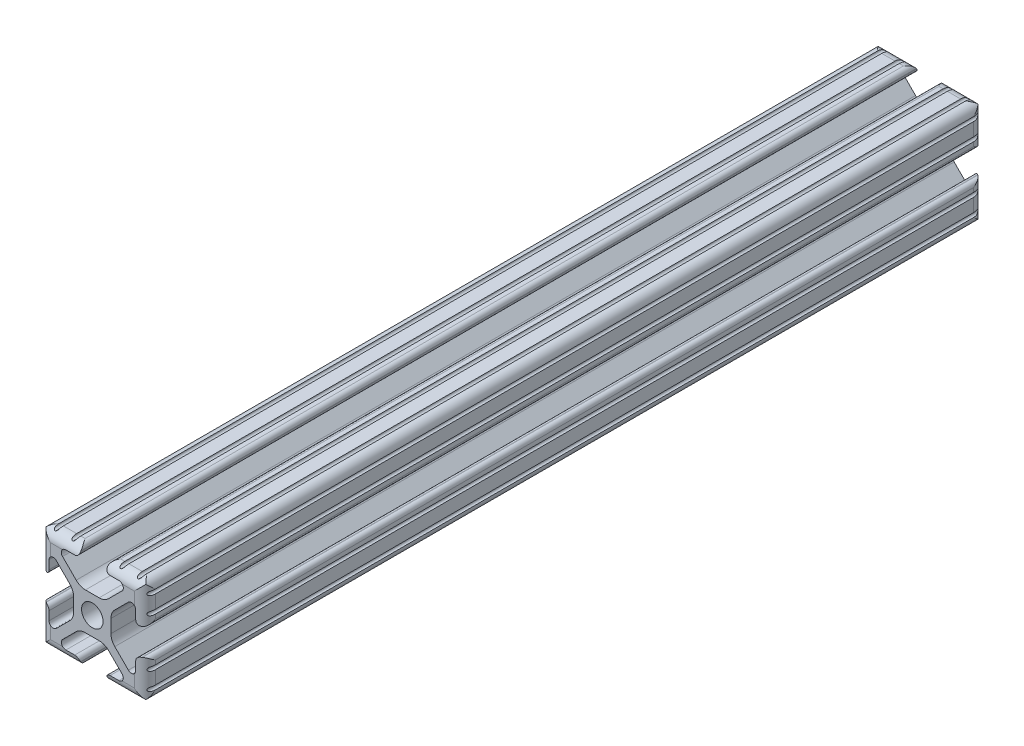
SolidWorks part; units mm, degrees
material "6061 Alloy"
ref_plane "Front Plane" through (0, 0, 0) normal (0, 0, 1) x (1, 0, 0)
ref_plane "Top Plane" through (0, 0, 0) normal (0, 1, 0) x (1, 0, 0)
ref_plane "Right Plane" through (0, 0, 0) normal (1, 0, 0) x (0, 0, -1)
sketch "Sketch1" plane through (0, 0, 0) normal (0, 0, 1) x (1, 0, 0)
  line L88 (-7.1797, -8.6452) -> (-3.9523, -5.4237)
  line L89 (-1.7093, -4.4958) -> (1.7093, -4.4958)
  line L90 (3.9523, -5.4237) -> (7.1797, -8.6452)
  line L91 (6.4164, -10.4902) -> (4.2875, -10.4902)
  line L92 (3.2385, -11.5392) -> (3.2385, -11.651)
  line L93 (4.2875, -12.7) -> (5.3171, -12.7)
  line L94 (6.3331, -12.7) -> (9.5504, -12.7)
  line L95 (12.7, -9.5504) -> (12.7, -6.3331)
  line L96 (12.7, -5.3171) -> (12.7, -4.2875)
  line L97 (11.651, -3.2385) -> (11.5392, -3.2385)
  line L98 (10.4902, -4.2875) -> (10.4902, -6.4021)
  line L99 (8.7371, -7.1294) -> (5.441, -3.8408)
  line L100 (4.5085, -1.5932) -> (4.5085, 1.5932)
  line L101 (5.441, 3.8408) -> (8.7371, 7.1294)
  line L102 (10.4902, 6.4021) -> (10.4902, 4.2875)
  line L103 (11.5392, 3.2385) -> (11.651, 3.2385)
  line L104 (12.7, 4.2875) -> (12.7, 5.3171)
  line L105 (12.7, 6.3331) -> (12.7, 9.5504)
  line L106 (9.5504, 12.7) -> (6.3331, 12.7)
  line L107 (5.3171, 12.7) -> (4.2875, 12.7)
  line L108 (3.2385, 11.651) -> (3.2385, 11.5392)
  line L109 (4.2875, 10.4902) -> (6.4768, 10.4902)
  line L110 (7.207, 8.7244) -> (3.8983, 5.4232)
  line L111 (1.6558, 4.4958) -> (-1.6558, 4.4958)
  line L112 (-3.8983, 5.4232) -> (-7.207, 8.7244)
  line L113 (-6.4768, 10.4902) -> (-4.2875, 10.4902)
  line L114 (-3.2385, 11.5392) -> (-3.2385, 11.651)
  line L115 (-4.2875, 12.7) -> (-5.3171, 12.7)
  line L116 (-6.3331, 12.7) -> (-9.5504, 12.7)
  line L117 (-12.7, 9.5504) -> (-12.7, 6.3331)
  line L118 (-12.7, 5.3171) -> (-12.7, 4.2875)
  line L119 (-11.651, 3.2385) -> (-11.5392, 3.2385)
  line L120 (-10.4902, 4.2875) -> (-10.4902, 6.4021)
  line L121 (-8.7371, 7.1294) -> (-5.441, 3.8408)
  line L122 (-4.5085, 1.5932) -> (-4.5085, -1.5932)
  line L123 (-5.441, -3.8408) -> (-8.7371, -7.1294)
  line L124 (-10.4902, -6.4021) -> (-10.4902, -4.2875)
  line L125 (-11.5392, -3.2385) -> (-11.651, -3.2385)
  line L126 (-12.7, -4.2875) -> (-12.7, -5.3171)
  line L127 (-12.7, -6.3331) -> (-12.7, -9.5504)
  line L128 (-9.5504, -12.7) -> (-6.3331, -12.7)
  line L129 (-5.3171, -12.7) -> (-4.2875, -12.7)
  line L130 (-3.2385, -11.651) -> (-3.2385, -11.5392)
  line L131 (-4.2875, -10.4902) -> (-6.4164, -10.4902)
  circle A1 centre (0, 0) radius 2.6035
  arc A104 (-7.1797, -8.6452) -> (-6.4164, -10.4902) centre (-6.4164, -9.4098) ccw
  arc A105 (-1.7093, -4.4958) -> (-3.9523, -5.4237) centre (-1.7093, -7.6708) ccw
  arc A106 (3.9523, -5.4237) -> (1.7093, -4.4958) centre (1.7093, -7.6708) ccw
  arc A107 (6.4164, -10.4902) -> (7.1797, -8.6452) centre (6.4164, -9.4098) ccw
  arc A108 (4.2875, -10.4902) -> (3.2385, -11.5392) centre (4.2875, -11.5392) ccw
  arc A109 (3.2385, -11.651) -> (4.2875, -12.7) centre (4.2875, -11.651) ccw
  arc A110 (6.3331, -12.7) -> (5.3171, -12.7) centre (5.8251, -12.7) ccw
  arc A111 (10.5664, -12.6998) -> (9.5504, -12.7) centre (10.0584, -12.7) ccw
  arc A112 (10.5664, -12.6998) -> (12.6998, -10.5664) centre (10.5918, -10.5918) ccw
  arc A113 (12.7, -9.5504) -> (12.6998, -10.5664) centre (12.7, -10.0584) ccw
  arc A114 (12.7, -5.3171) -> (12.7, -6.3331) centre (12.7, -5.8251) ccw
  arc A115 (12.7, -4.2875) -> (11.651, -3.2385) centre (11.651, -4.2875) ccw
  arc A116 (11.5392, -3.2385) -> (10.4902, -4.2875) centre (11.5392, -4.2875) ccw
  arc A117 (8.7371, -7.1294) -> (10.4902, -6.4021) centre (9.4628, -6.4021) ccw
  arc A118 (4.5085, -1.5932) -> (5.441, -3.8408) centre (7.6835, -1.5932) ccw
  arc A119 (5.441, 3.8408) -> (4.5085, 1.5932) centre (7.6835, 1.5932) ccw
  arc A120 (10.4902, 6.4021) -> (8.7371, 7.1294) centre (9.4628, 6.4021) ccw
  arc A121 (10.4902, 4.2875) -> (11.5392, 3.2385) centre (11.5392, 4.2875) ccw
  arc A122 (11.651, 3.2385) -> (12.7, 4.2875) centre (11.651, 4.2875) ccw
  arc A123 (12.7, 6.3331) -> (12.7, 5.3171) centre (12.7, 5.8251) ccw
  arc A124 (12.6998, 10.5664) -> (12.7, 9.5504) centre (12.7, 10.0584) ccw
  arc A125 (12.6998, 10.5664) -> (10.5664, 12.6998) centre (10.5918, 10.5918) ccw
  arc A126 (9.5504, 12.7) -> (10.5664, 12.6998) centre (10.0584, 12.7) ccw
  arc A127 (5.3171, 12.7) -> (6.3331, 12.7) centre (5.8251, 12.7) ccw
  arc A128 (4.2875, 12.7) -> (3.2385, 11.651) centre (4.2875, 11.651) ccw
  arc A129 (3.2385, 11.5392) -> (4.2875, 10.4902) centre (4.2875, 11.5392) ccw
  arc A130 (7.207, 8.7244) -> (6.4768, 10.4902) centre (6.4768, 9.4563) ccw
  arc A131 (1.6558, 4.4958) -> (3.8983, 5.4232) centre (1.6558, 7.6708) ccw
  arc A132 (-3.8983, 5.4232) -> (-1.6558, 4.4958) centre (-1.6558, 7.6708) ccw
  arc A133 (-6.4768, 10.4902) -> (-7.207, 8.7244) centre (-6.4768, 9.4563) ccw
  arc A134 (-4.2875, 10.4902) -> (-3.2385, 11.5392) centre (-4.2875, 11.5392) ccw
  arc A135 (-3.2385, 11.651) -> (-4.2875, 12.7) centre (-4.2875, 11.651) ccw
  arc A136 (-6.3331, 12.7) -> (-5.3171, 12.7) centre (-5.8251, 12.7) ccw
  arc A137 (-10.5664, 12.6998) -> (-9.5504, 12.7) centre (-10.0584, 12.7) ccw
  arc A138 (-10.5664, 12.6998) -> (-12.6998, 10.5664) centre (-10.5918, 10.5918) ccw
  arc A139 (-12.7, 9.5504) -> (-12.6998, 10.5664) centre (-12.7, 10.0584) ccw
  arc A140 (-12.7, 5.3171) -> (-12.7, 6.3331) centre (-12.7, 5.8251) ccw
  arc A141 (-12.7, 4.2875) -> (-11.651, 3.2385) centre (-11.651, 4.2875) ccw
  arc A142 (-11.5392, 3.2385) -> (-10.4902, 4.2875) centre (-11.5392, 4.2875) ccw
  arc A143 (-8.7371, 7.1294) -> (-10.4902, 6.4021) centre (-9.4628, 6.4021) ccw
  arc A144 (-4.5085, 1.5932) -> (-5.441, 3.8408) centre (-7.6835, 1.5932) ccw
  arc A145 (-5.441, -3.8408) -> (-4.5085, -1.5932) centre (-7.6835, -1.5932) ccw
  arc A146 (-10.4902, -6.4021) -> (-8.7371, -7.1294) centre (-9.4628, -6.4021) ccw
  arc A147 (-10.4902, -4.2875) -> (-11.5392, -3.2385) centre (-11.5392, -4.2875) ccw
  arc A148 (-11.651, -3.2385) -> (-12.7, -4.2875) centre (-11.651, -4.2875) ccw
  arc A149 (-12.7, -6.3331) -> (-12.7, -5.3171) centre (-12.7, -5.8251) ccw
  arc A150 (-12.6998, -10.5664) -> (-12.7, -9.5504) centre (-12.7, -10.0584) ccw
  arc A151 (-12.6998, -10.5664) -> (-10.5664, -12.6998) centre (-10.5918, -10.5918) ccw
  arc A152 (-9.5504, -12.7) -> (-10.5664, -12.6998) centre (-10.0584, -12.7) ccw
  arc A153 (-5.3171, -12.7) -> (-6.3331, -12.7) centre (-5.8251, -12.7) ccw
  arc A154 (-4.2875, -12.7) -> (-3.2385, -11.651) centre (-4.2875, -11.651) ccw
  arc A155 (-3.2385, -11.5392) -> (-4.2875, -10.4902) centre (-4.2875, -11.5392) ccw
extrude "Boss-Extrude1" add sketch "Sketch1" along normal mid plane 203.2
sketch "Sketch3" plane through (-12.7, 0, 0) normal (-1, 0, 0) x (0, 0, 1)
  line L0 (-101.6, 0) -> (101.6, 0) construction
  line L1 (101.6, -12.6998) -> (-101.6, -12.6998) construction
  line L2 (101.6, -12.6998) -> (101.6, 12.6998) construction
  line L3 (101.6, 12.6998) -> (-101.6, 12.6998) construction
  line L4 (-101.6, -12.6998) -> (-101.6, 12.6998) construction
  circle A0 centre (69.85, 0) radius 3.175
  circle A1 centre (50.8, 0) radius 3.175
  dimension "D1" = 31.75
  dimension "D3" = 6.35
  dimension "D2" = 19.05
fillet "Fillet1" radius 2.54 16 edges at (-12.7, 7.9417, 101.6) (-7.9418, 12.7, 101.6) (7.9418, 12.7, 101.6) (12.7, 7.9417, 101.6) (12.7, -7.9417, 101.6) (7.9418, -12.7, 101.6) (-7.9418, -12.7, 101.6) (-12.7, -7.9417, 101.6) (12.7, 7.9417, -101.6) (12.7, -7.9417, -101.6) (7.9418, -12.7, -101.6) (-7.9418, -12.7, -101.6) (-12.7, -7.9417, -101.6) (-12.7, 7.9417, -101.6) (-7.9418, 12.7, -101.6) (7.9418, 12.7, -101.6)
extrude "Cut-Extrude1" cut sketch "Sketch3" against normal through all
